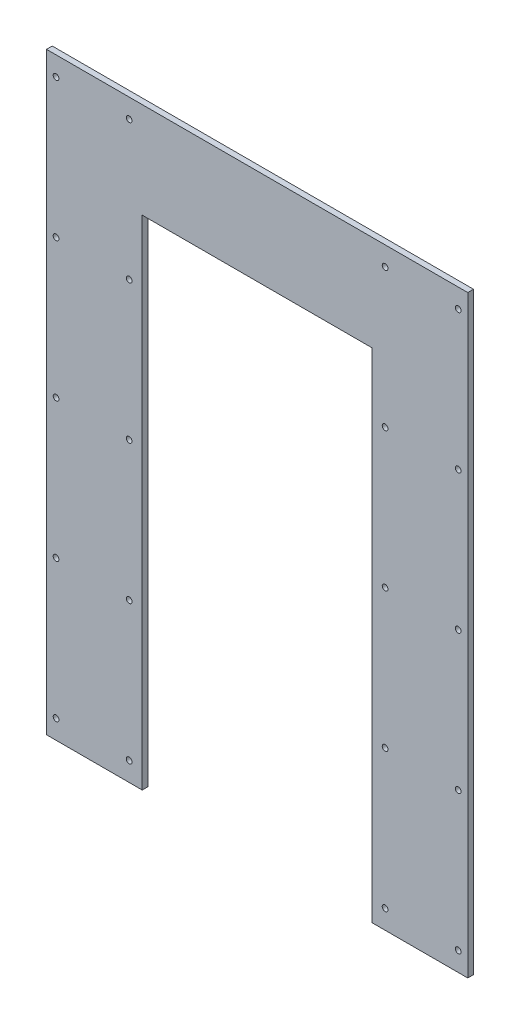
SolidWorks part; units mm, degrees
ref_plane "Plan de face" through (0, 0, 0) normal (0, 0, 1) x (1, 0, 0)
ref_plane "Plan de dessus" through (0, 0, 0) normal (0, 1, 0) x (1, 0, 0)
ref_plane "Plan de droite" through (0, 0, 0) normal (1, 0, 0) x (0, 0, -1)
sketch "Esquisse1" plane through (0, 0, 0) normal (0, 0, 1) x (1, 0, 0)
  line L0 (85, 155) -> (85, -155) construction
  line L5 (25, -155) -> (-25, -155)
  line L6 (25, -155) -> (25, 105)
  line L15 (25, 155) -> (-25, 155)
  line L16 (-25, -155) -> (-25, 155)
  line L17 (25, -155) -> (-25, 155) construction
  line L18 (25, 155) -> (-25, -155) construction
  line L19 (25, 155) -> (145, 155)
  line L21 (25, 105) -> (145, 105)
  line L23 (145, 155) -> (195, -155) construction
  line L24 (145, -155) -> (195, 155) construction
  line L26 (195, -155) -> (195, 155)
  line L27 (145, 155) -> (195, 155)
  line L28 (145, -155) -> (145, 105)
  line L29 (145, -155) -> (195, -155)
  point P0 (0, 0)
  point P15 (170, 0)
  dimension "D3" = 60
  dimension "D1" = 50
  dimension "D2" = 310
extrude "Boss.-Extru.1" add sketch "Esquisse1" along normal blind 3 contours L15 L16 L5 L6 region at (0, -151.1987, 0)
sketch "Esquisse2" plane through (0, 0, 3) normal (0, 0, 1) x (1, 0, 0)
  line L0 (-20, 155) -> (-20, -155) construction
  line L1 (195, 155) -> (-25, 155) construction
  line L2 (25, -155) -> (-25, -155) construction
  line L3 (0, -155) -> (0, 155) construction
  line L4 (20, 155) -> (20, -155) construction
  line L5 (-25, 155) -> (195, 155) construction
  line L6 (85, 155) -> (85, -155) construction
  line L7 (150, 155) -> (150, -155) construction
  line L8 (170, -155) -> (170, 155) construction
  line L9 (190, 155) -> (190, -155) construction
  line L10 (-25, -155) -> (-25, 155) construction
  line L11 (25, -155) -> (25, 105) construction
  circle A0 centre (-20, -145) radius 1.5
  circle A1 centre (-20, -72.5) radius 1.5
  circle A2 centre (-20, 0) radius 1.5
  circle A3 centre (-20, 72.5) radius 1.5
  circle A4 centre (-20, 145) radius 1.5
  circle A5 centre (18.1668, 145) radius 1.5
  circle A6 centre (18.1668, 72.5) radius 1.5
  circle A7 centre (18.1668, 0) radius 1.5
  circle A8 centre (18.1668, -72.5) radius 1.5
  circle A9 centre (18.1668, -145) radius 1.5
  circle A10 centre (151.8332, -145) radius 1.5
  circle A11 centre (151.8332, -72.5) radius 1.5
  circle A12 centre (151.8332, 0) radius 1.5
  circle A13 centre (151.8332, 72.5) radius 1.5
  circle A14 centre (151.8332, 145) radius 1.5
  circle A15 centre (190, 145) radius 1.5
  circle A16 centre (190, 72.5) radius 1.5
  circle A17 centre (190, 0) radius 1.5
  circle A18 centre (190, -72.5) radius 1.5
  circle A19 centre (190, -145) radius 1.5
  dimension "D1" = 3
  dimension "D3" = 10
  dimension "D4" = 10
  dimension "D5" = 5
  dimension "D6" = 5
  dimension "D2" = 5
extrude "Enlèv. mat.-Extru.1" cut sketch "Esquisse2" against normal up to next
